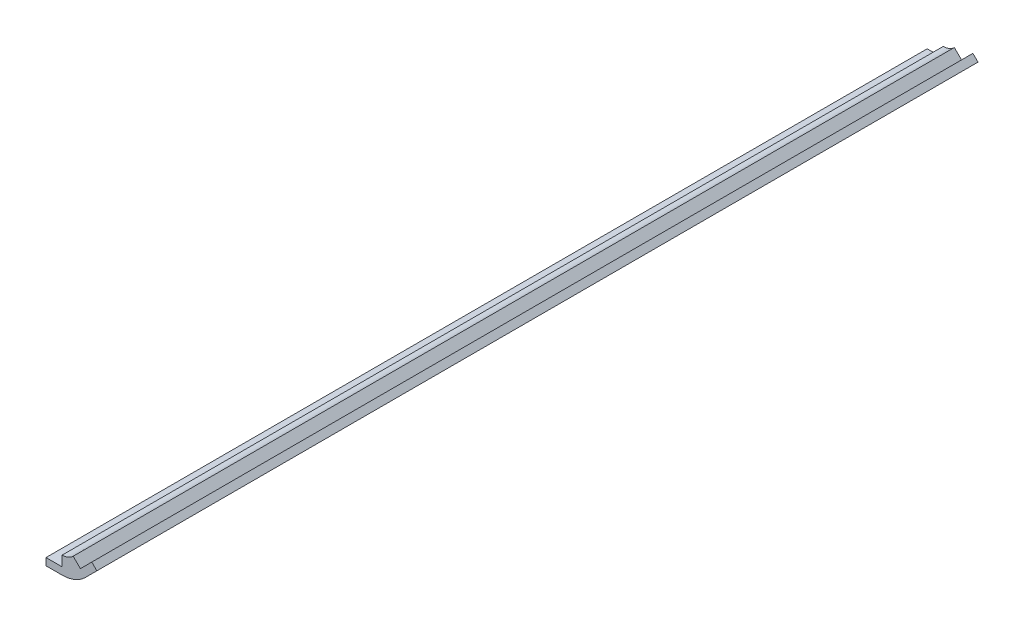
SolidWorks part; units mm, degrees
ref_plane "Front Plane" through (0, 0, 0) normal (0, 0, 1) x (1, 0, 0)
ref_plane "Top Plane" through (0, 0, 0) normal (0, 1, 0) x (1, 0, 0)
ref_plane "Right Plane" through (0, 0, 0) normal (1, 0, 0) x (0, 0, -1)
ref_axis "Axis1" through (0, 0, -88.99) along (0, 0, 1)
sketch "Sketch16" plane through (0, 0, 0) normal (0, 1, 0) x (1, 0, 0)
  line L0 (0, -127) -> (0, 127) construction
  point P2 (0, 0)
  dimension "D1" = 254
sketch "Sketch2" plane through (0, 0, 0) normal (0, 0, 1) x (1, 0, 0)
  line L0 (-7.3025, -1.5) -> (-2.54, -1.5) construction
  line L1 (-7.3025, -1.5) -> (-7.3025, 1.5) construction
  line L2 (-2.54, -1.5) -> (-2.54, 1.5) construction
  line L3 (-7.3025, 1.5) -> (-2.54, 1.5) construction
  line L4 (-2.54, 0) -> (0, 0) construction
  line L5 (0, 0) -> (1.7961, 1.7961) construction
  line L6 (2.8567, 0.7354) -> (0.7354, 2.8567) construction
  line L7 (2.8567, 0.7354) -> (6.2243, 4.103) construction
  line L8 (0.7354, 2.8567) -> (4.103, 6.2243) construction
  line L9 (6.2243, 4.103) -> (4.103, 6.2243) construction
  point P7 (1.7961, 1.7961)
  point P16 (-0.6213, 1.5)
  dimension "D1" = 3
  dimension "D2" = 4.7625
  dimension "D3" = 2.54
  dimension "D4" = 135
ref_plane "Plane1" through (0, 0, 0) normal (-0.7071, 0.7071, 0) x (0.7071, 0.7071, 0)
sketch "Sketch7" plane through (0, 0, 0) normal (0, 0, 1) x (1, 0, 0)
  line L0 (-7.3025, -1.5) -> (-2.54, -1.5)
  line L1 (-7.3025, -1.5) -> (-7.3025, -3.6212)
  line L2 (-2.54, -1.5) -> (-2.54, -3.6212)
  line L3 (-7.3025, -3.6212) -> (-2.54, -3.6212)
  dimension "D1" = 2.1212
extrude "Boss-Extrude2" add sketch "Sketch7" along normal mid plane 260.35 separate body
sketch "Sketch8" plane through (0, 0, 0) normal (0, 0, 1) x (1, 0, 0)
  line L0 (2.8567, 0.7354) -> (6.2243, 4.103)
  line L1 (2.8567, 0.7354) -> (4.3566, -0.7645)
  line L2 (6.2243, 4.103) -> (7.7242, 2.6031)
  line L3 (4.3566, -0.7645) -> (7.7242, 2.6031)
  line L4 (-2.54, -3.6212) -> (-2.54, -1.5) construction
extrude "Boss-Extrude3" add sketch "Sketch8" along normal mid plane 260.35
sketch "Sketch11" plane through (0, 0, 0) normal (0, 0, 1) x (1, 0, 0)
  line L1 (-2.54, -1.5) -> (-7.3025, -1.5)
  line L2 (-7.3025, -1.5) -> (-7.3025, -3.6212)
  line L8 (7.7242, 2.6031) -> (6.2243, 4.103)
  line L9 (6.2243, 4.103) -> (2.8567, 0.7354)
  line L13 (2.8567, 0.7354) -> (0.7354, 2.8567)
  line L14 (0.7354, 2.8567) -> (-0.6213, 1.5) construction
  line L15 (-0.6213, 1.5) -> (-2.54, 1.5) construction
  line L17 (-2.54, 1.5) -> (-2.54, -1.5)
  line L18 (7.7242, 2.6031) -> (4.3566, -0.7645)
  line L19 (2.8567, 0.7354) -> (4.3566, -0.7645) construction
  line L20 (-2.54, -3.6212) -> (-7.3025, -3.6212)
  arc A0 (0.7354, 2.8567) -> (-2.54, 1.5) centre (-2.54, 6.1321) cw
  arc A1 (4.3566, -0.7645) -> (-2.54, -3.6212) centre (-2.54, 6.1321) cw
extrude "Boss-Extrude4" add sketch "Sketch11" along normal mid plane 260.35
ref_plane "Midplane" through (0, 0, 0) normal (0.9239, 0.3827, 0) x (0.3827, -0.9239, 0)
equation "\"plate_thickness\"= 3mm"
equation "\"D1@Sketch2\"=\"plate_thickness\""
equation "\"joiner_lip_width\"= .1875"
equation "\"D2@Sketch2\"=\"joiner_lip_width\""
equation "\"face_gap\"=0.1"
equation "\"D3@Sketch2\"=\"face_gap\""
equation "\"inside_angle\"= 135deg"
equation "\"joiner_thickness\"= 0.0835128"
equation "\"edge_length\"= 10"
equation "\"Face1_TopLip\"= \"angle\" * 2"
equation "\"Face1_BottomLip\"= \"angle\" * 2"
equation "\"Face2_TopLip\"= 45deg"
equation "\"Face2_BottomLip\"= 45deg"
equation "\"D1@Sketch7\"=\"joiner_thickness\""
equation "\"D1@Boss-Extrude2\"=\"Extrude_to\""
equation "\"D1@Boss-Extrude3\"=\"Extrude_to\""
equation "\"D1@Boss-Extrude4\"=\"Extrude_to\""
equation "\"Extrude_to\"= \"edge_length\" + .25"
equation "\"D1@Sketch16\"=\"edge_length\""
equation "\"angle\"= atn ( 0.1 / ( ( 3.7085 - 3.0793 ) / 2 ) )"
equation "\"D4@Sketch2\"=\"inside_angle\""
equation "\"D2@Sketch5\"=\"Face2_TopLip\"/2"
equation "\"D1@Sketch5\"=\"Face2_BottomLip\"/2"
equation "\"D2@Sketch4\"=\"Face1_TopLip\"/2"
equation "\"D1@Sketch4\"=\"Face1_BottomLip\"/2"
equation "\"D1\" = \"edge_length\""
equation "\"D2@Sketch12\"=\"Face1_TopLip\"/2"
equation "\"D1@Sketch12\"=\"Face1_BottomLip\"/2"
